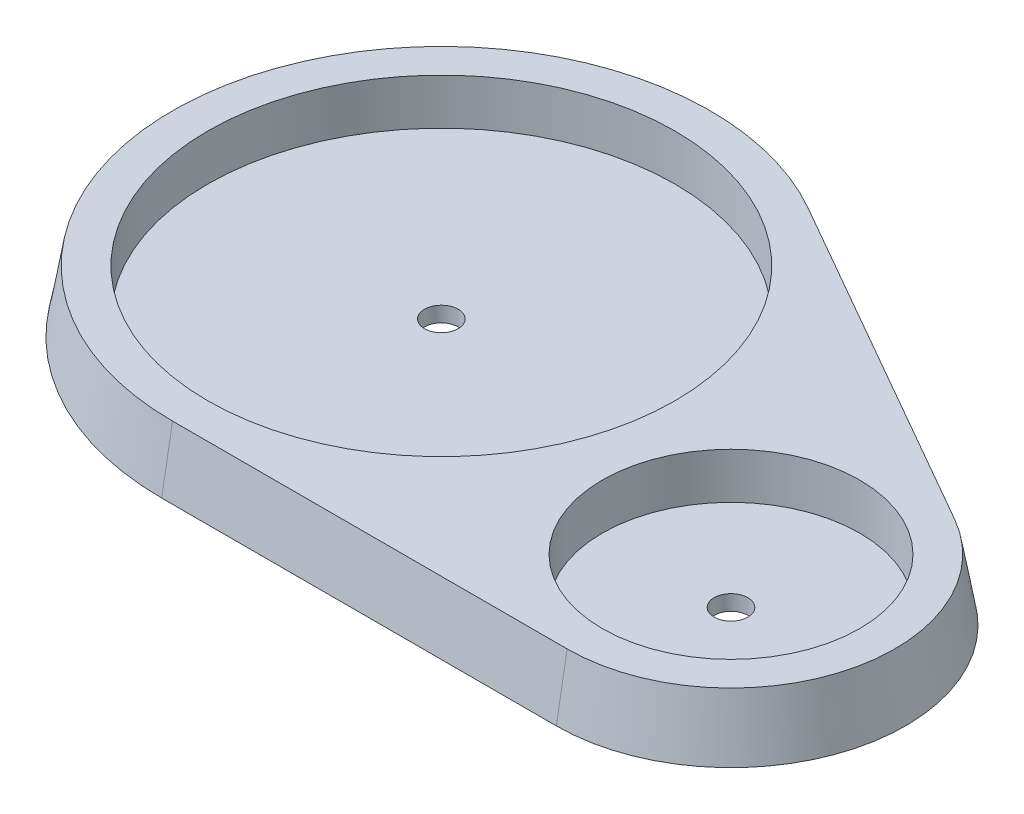
SolidWorks part; units mm, degrees
ref_plane "Front Plane" through (0, 0, 0) normal (0, 0, 1) x (1, 0, 0)
ref_plane "Top Plane" through (0, 0, 0) normal (0, 1, 0) x (1, 0, 0)
ref_plane "Right Plane" through (0, 0, 0) normal (1, 0, 0) x (0, 0, -1)
sketch "Sketch1" plane through (0, 0, 0) normal (0, 1, 0) x (1, 0, 0)
  line L0 (31.4181, 3.0437) -> (9.0666, 15.8385)
  line L1 (0, -18.25) -> (25.7546, -18.25)
  circle A0 centre (0, 0) radius 15.25
  circle A1 centre (25.7546, -6.85) radius 8.4
  circle A2 centre (0, 0) radius 18.25
  circle A3 centre (25.7546, -6.85) radius 11.4
  circle A4 centre (0, 0) radius 1.1
  circle A5 centre (25.7546, -6.85) radius 1.1
  dimension "D1" = 30.5
  dimension "D2" = 16.8
  dimension "D4" = 36.5
  dimension "D5" = 22.8
  dimension "D6" = 2.2
  dimension "D7" = 2.2
  dimension "D3" = 26.65
extrude "Boss-Extrude1" add sketch "Sketch1" along normal blind 4 draft 10 contours A3 A2 A0 | A3 A0 | A0 A3 | A2 A3 A0 A1 | A1 A2 | A3 L0 A2 | A3 A2 A1 | A2 A1 | A3 A2 L1 | A4 | A5 region at (19.9442, 0, -7.1213) region at (26.8126, 0, -1.2436) region at (35.3414, 0, 1.2914) region at (-14.6937, 0, -1.9207) region at (14.92, 0, -9.5865) region at (16.2557, 0, 4.3235) region at (13.771, 0, 16.0886) region at (0, 0, 0) region at (25.7546, 0, 6.85)
extrude "Cut-Extrude2" cut sketch "Sketch1<5>" against normal blind 4 from surface contours A4 | A5 region at (0, 0, 0) region at (25.7546, 0, 6.85) starting at face at (12.976, 4, 3.4513)
sketch "Sketch1<5>" plane through (0, 0, 0) normal (0, 1, 0) x (1, 0, 0) same geometry as "Sketch1"
extrude "Cut-Extrude3" cut sketch "Sketch1<6>" against normal blind 3 from surface contours A0 A4 | A1 A5 region at (26.8126, 0, -1.2436) region at (-14.6937, 0, -1.9207) starting at face at (0, 4, 1.1)
sketch "Sketch1<6>" plane through (0, 0, 0) normal (0, 1, 0) x (1, 0, 0) same geometry as "Sketch1"
